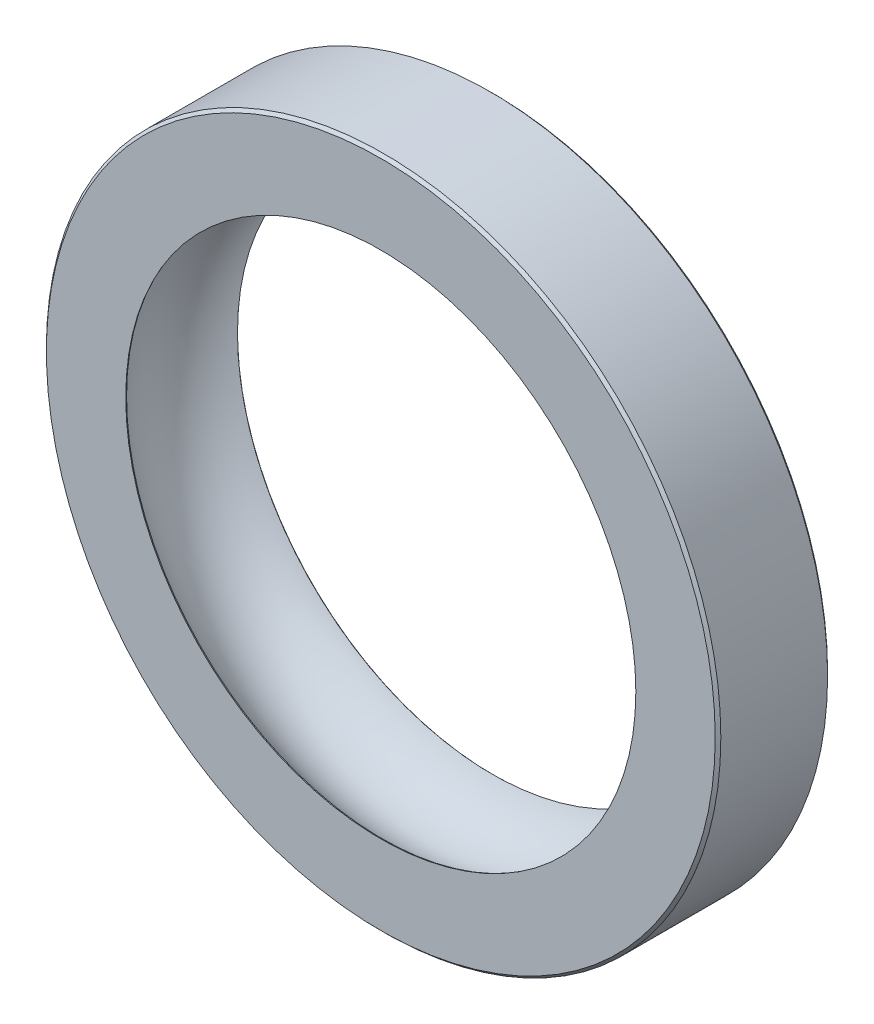
SolidWorks part; units mm, degrees
ref_plane "Front Plane" through (0, 0, 0) normal (0, 0, 1) x (1, 0, 0)
ref_plane "Top Plane" through (0, 0, 0) normal (0, 1, 0) x (1, 0, 0)
ref_plane "Right Plane" through (0, 0, 0) normal (1, 0, 0) x (0, 0, -1)
sketch "Sketch1" plane through (0, 0, 0) normal (0, 0, 1) x (1, 0, 0)
  circle A0 centre (0, 0) radius 30
  dimension "D1" = 60
extrude "Bearing Diameter" add sketch "Sketch1" along normal blind 10
sketch "Sketch2" plane through (0, 0, 10) normal (0, 0, 1) x (1, 0, 0)
  circle A0 centre (0, 0) radius 22.5
  dimension "D1" = 45
extrude "Bearing Inner Diameter" cut sketch "Sketch2" against normal through all both and the other way through all
sketch "Sketch3" plane through (0, 0, 0) normal (0, 1, 0) x (1, 0, 0)
  line L0 (0, 0) -> (0, -10) construction
  line L1 (-30, -10) -> (30, -10) construction
  line L2 (-22.5, 0) -> (-22.5, -10)
  line L5 (-22.5, 0) -> (-22.5, -10) construction
  line L6 (-22.5, -10) -> (22.5, -10) construction
  arc A2 (-22.5, 0) -> (-22.5, -10) centre (-20.2087, -5) ccw
  dimension "D1" = 5.5
revolve "Cut-Revolve2" cut sketch "Sketch3" angle 360 about L0 region at (-23.8222, 0, 5)
chamfer "Chamfer1" distance 0.25 angle 45 4 edges at (30, 0, 0) (-22.5, 0, 0) (30, 0, 10) (-22.5, 0, 10) first distance on face at (-22.5, 0, 0) first distance on face at (30, 0, 10) first distance on face at (-22.5, 0, 10)
sketch "Sketch4" plane through (0, 0, 0) normal (0, 1, 0) x (1, 0, 0)
  line L0 (-25.7086, -4.9657) -> (25.7086, -4.9657) construction
  arc A0 (-22.669, -0.081) -> (-22.7302, -9.888) centre (-20.2087, -5) ccw construction
  arc A1 (22.7302, -9.888) -> (22.669, -0.081) centre (20.2087, -5) ccw construction
  dimension "D1" = 51.4172
